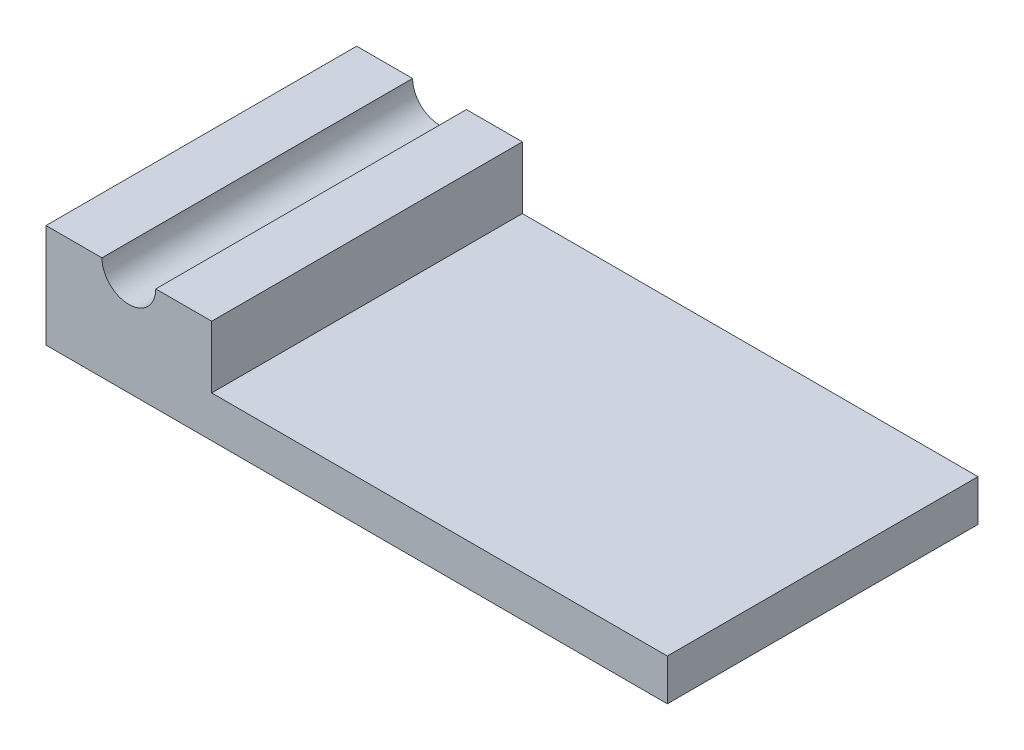
SolidWorks part; units mm, degrees
ref_plane "Front Plane" through (0, 0, 0) normal (0, 0, 1) x (1, 0, 0)
ref_plane "Top Plane" through (0, 0, 0) normal (0, 1, 0) x (1, 0, 0)
ref_plane "Right Plane" through (0, 0, 0) normal (1, 0, 0) x (0, 0, -1)
sketch "Sketch2" plane through (0, 0, 0) normal (0, 0, 1) x (1, 0, 0)
  line L0 (0, 0) -> (0, 5)
  line L1 (0, 5) -> (2.7, 5)
  line L2 (30, 2) -> (30, 5) construction
  line L3 (30, 0) -> (30, 2)
  line L4 (30, 5) -> (8, 5) construction
  line L5 (5.3, 5) -> (8, 5)
  line L6 (8, 5) -> (8, 2)
  line L7 (8, 2) -> (30, 2)
  line L8 (15, 2) -> (15, 0) construction
  line L9 (30, 0) -> (0, 0)
  line L10 (2.7, 5) -> (5.3, 5) construction
  line L11 (19, 5) -> (19, 2) construction
  arc A0 (2.7, 5) -> (5.3, 5) centre (4, 5) ccw
  dimension "D1" = 15
  dimension "D2" = 5
  dimension "D3" = 2
  dimension "D4" = 8
  dimension "D5" = 2.7
  dimension "D6" = 2.7
extrude "Boss-Extrude1" add sketch "Sketch2" along normal blind 15
sketch "Sketch3" plane through (0, 0, 0) normal (0, -1, 0) x (1, 0, 0)
  line L0 (0, 15) -> (30, 0) construction
  circle A0 centre (15, 7.5) radius 1.75
  dimension "D1" = 3.5
extrude "Cut-Extrude1" cut sketch "Sketch3" against normal blind 1
chamfer "Chamfer1" distance 0.5 angle 45 2 edges at (15, 0, 5.75) (15, 1, 5.75)
ref_plane "Plane1" through (0, 0, 7.5) normal (0, 0, -1) x (-1, 0, 0)
